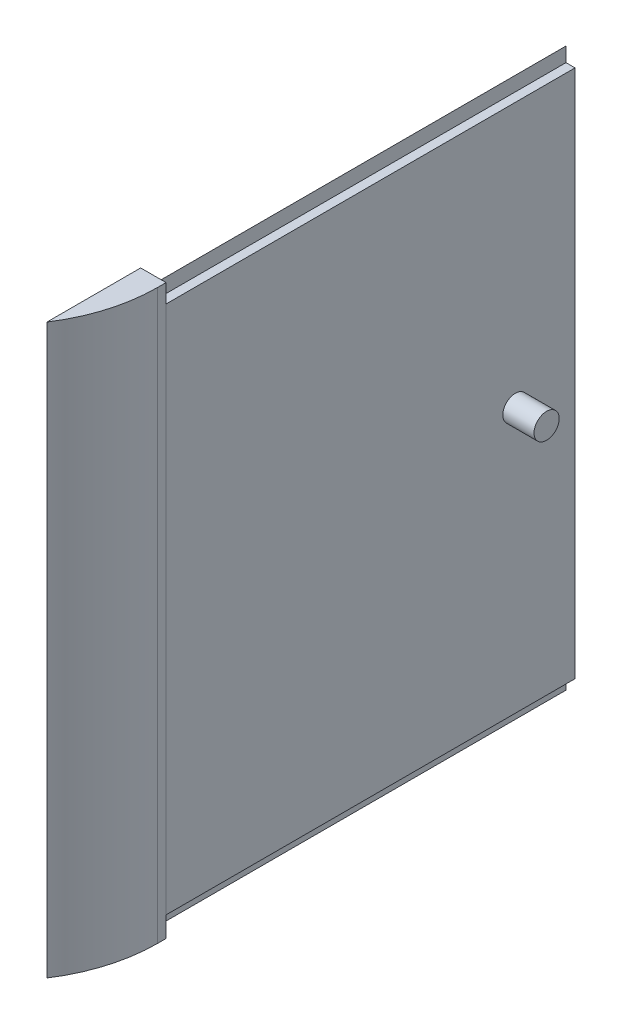
SolidWorks part; units mm, degrees
ref_plane "Front Plane" through (0, 0, 0) normal (0, 0, 1) x (1, 0, 0)
ref_plane "Top Plane" through (0, 0, 0) normal (0, 1, 0) x (1, 0, 0)
ref_plane "Right Plane" through (0, 0, 0) normal (1, 0, 0) x (0, 0, -1)
sketch "Sketch1" plane through (0, 0, 0) normal (0, 0, 1) x (1, 0, 0)
  line L0 (33.6841, -148) -> (37.6841, -148) construction
  line L1 (37.6841, -12) -> (37.6841, -7.95) construction
  line L2 (37.6841, -7.95) -> (33.6841, -12) construction
  line L3 (37.6841, -12) -> (33.6841, -12) construction
  line L4 (37.4341, -12) -> (37.4341, -8.5589)
  line L5 (37.4341, -8.5589) -> (33.9341, -12.1026)
  line L6 (37.6841, -147.75) -> (39.75, -147.75)
  line L7 (39.75, -12.25) -> (39.75, -147.75)
  line L8 (37.6841, -148) -> (40, -148) construction
  line L9 (37.6841, -152.05) -> (37.6841, -148) construction
  line L11 (33.6841, -148) -> (37.6841, -152.05) construction
  line L12 (37.6841, -12) -> (40, -12) construction
  line L16 (40, -12) -> (40, -148) construction
  line L18 (33.6841, -12) -> (33.6841, -148) construction
  line L19 (37.6841, -12.25) -> (39.75, -12.25)
  line L20 (33.9341, -147.8974) -> (37.4341, -151.4411)
  line L21 (37.4341, -151.4411) -> (37.4341, -148)
  line L22 (33.9341, -12.1026) -> (33.9341, -147.8974)
  line L23 (37.4341, -8.5589) -> (33.8619, -12.1757) construction
  line L24 (37.6841, -12.25) -> (37.4341, -12.25)
  line L25 (37.4341, -12) -> (37.4341, -12.25)
  line L26 (37.4341, -148) -> (37.4341, -147.75)
  line L27 (37.4341, -147.75) -> (37.6841, -147.75)
  line L29 (33.8619, -147.8243) -> (37.4341, -151.4411) construction
  line L30 (33.9341, -12) -> (33.9341, -148) construction
  line L31 (37.6841, -12.25) -> (33.6841, -12.25) construction
  dimension "D1" = 4.05
  dimension "D2" = 4
  dimension "D3" = 0.25
extrude "Boss-Extrude1" add sketch "Sketch1" against normal blind 105
sketch "Sketch4" plane through (0, 0, 0) normal (0, 0, 1) x (1, 0, 0)
  line L1 (40, -152.75) -> (33.5, -152.75)
  line L3 (40, -7.25) -> (33.5, -7.25)
  line L4 (33.5, -152.75) -> (33.5, -7.25)
  line L5 (40, -80) -> (33.5, -80) construction
  line L6 (40, -7.25) -> (40, -80)
  line L7 (40, -80) -> (40, -152.75)
  dimension "D1" = 145.5
  dimension "D2" = 6.5
extrude "Boss-Extrude2" add sketch "Sketch4" along normal blind 24
fillet "Fillet1" radius 40 1 edges at (40, -80, 24)
sketch "Sketch5" plane through (39.75, 0, 0) normal (1, 0, 0) x (0, 0, -1)
  line L0 (89.7148, -12) -> (89.7148, -148) construction
  circle A0 centre (89.7148, -80) radius 3.2191
extrude "Boss-Extrude3" add sketch "Sketch5" along normal blind 8
